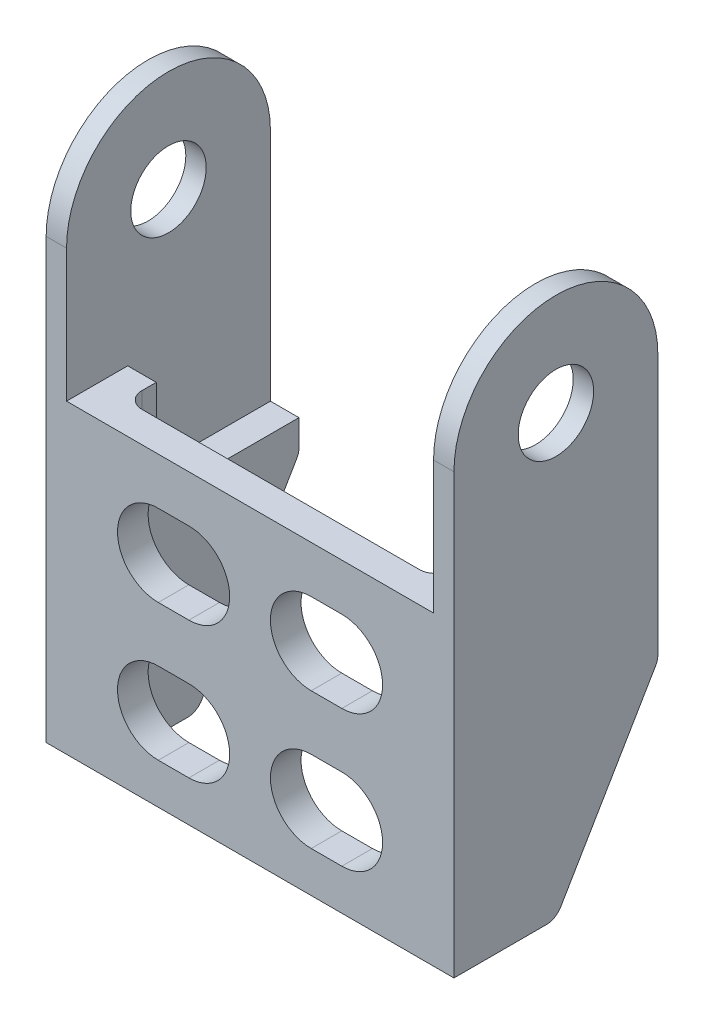
SolidWorks part; units mm, degrees
material "PLA+"
ref_plane "Front Plane" through (0, 0, 0) normal (0, 0, 1) x (1, 0, 0)
ref_plane "Top Plane" through (0, 0, 0) normal (0, 1, 0) x (1, 0, 0)
ref_plane "Right Plane" through (0, 0, 0) normal (1, 0, 0) x (0, 0, -1)
sketch "Sketch1" plane through (0, 0, 0) normal (0, 0, 1) x (1, 0, 0)
  line L1 (10, -7.5) -> (-10, -7.5)
  line L2 (10, -7.5) -> (10, 7.5)
  line L3 (10, 7.5) -> (-10, 7.5)
  line L4 (-10, -7.5) -> (-10, 7.5)
  line L5 (10, -7.5) -> (-10, 7.5) construction
  line L6 (10, 7.5) -> (-10, -7.5) construction
  point P0 (0, 0)
  dimension "D1" = 20
  dimension "D2" = 15
extrude "Boss-Extrude1" add sketch "Sketch1" along normal blind 1.5
sketch "Sketch2" plane through (10, 0, 0) normal (1, 0, 0) x (0, 0, -1)
  line L0 (-1.5, -7.5) -> (3.5, -7.5)
  line L1 (3.5, -7.5) -> (8.5, 1)
  line L2 (8.5, 1) -> (8.5, 14)
  line L4 (-1.5, 14) -> (-1.5, 7.5)
  arc A0 (8.5, 14) -> (-1.5, 14) centre (3.5, 14) ccw
  circle A1 centre (3.5, 14) radius 1.85
  point P9 (3.5, 19)
  line M1 (0, -7.5) -> (0, 7.5)
  line M2 (0, 7.5) -> (-1.5, 7.5)
  dimension "D3" = 10
  dimension "D5" = 3.7
  dimension "D1" = 10
  dimension "D2" = 5
  dimension "D4" = 26.5
  dimension "D6" = 8.5
extrude "Boss-Extrude2" add sketch "Sketch2" against normal blind 2.4 contours L2 A0 L4 L0 L1 A1 M2 M1 region at (10, 6.4099, -3.6241)
sketch "Sketch3" plane through (7.6, 0, 0) normal (-1, 0, 0) x (0, 0, 1)
  line L0 (1.5, 7.5) -> (-1.5, 7.5)
  line L1 (-1.5, 7.5) -> (-1.5, 5.5)
  line L2 (-4.5, 2.5) -> (-8.5, 2.5)
  line L3 (-8.5, 2.5) -> (-8.5, 19.0437)
  line L4 (-8.5, 19.0437) -> (1.5, 19.0437)
  line L5 (1.5, 19.0437) -> (1.5, 7.5)
  line L6 (-8.5, 1) -> (-8.5, 14) construction
  line L7 (0, -7.5) -> (-3.5, -7.5) construction
  arc A0 (-4.5, 2.5) -> (-1.5, 5.5) centre (-4.5, 5.5) ccw
  dimension "D1" = 3
  dimension "D2" = 10
  dimension "D3" = 3
extrude "Cut-Extrude1" cut sketch "Sketch3" against normal blind 1.4
mirror "Mirror1" about plane through (0, 0, 0) normal (1, 0, 0) of "Cut-Extrude1", "Boss-Extrude2", "Boss-Extrude1"
fillet "Fillet1" radius 0.8 6 edges at (-8.8, 1, -8.5) (8.8, 1, -8.5) (8.8, -7.5, -3.5) (-8.8, -7.5, -3.5) (-7.6, 0, 0) (7.6, 0, 0)
sketch "Sketch4" plane through (0, 0, 1.5) normal (0, 0, 1) x (1, 0, 0)
  line L0 (-4.5, 3.2) -> (-3, 3.2) construction
  line L1 (-4.5, 5.2) -> (-3, 5.2)
  line L2 (-4.5, 1.2) -> (-3, 1.2)
  line L3 (3, 3.2) -> (4.5, 3.2) construction
  line L4 (3, 5.2) -> (4.5, 5.2)
  line L5 (3, 1.2) -> (4.5, 1.2)
  line L6 (-4.5, -3.5) -> (-3, -3.5) construction
  line L7 (-4.5, -1.5) -> (-3, -1.5)
  line L8 (-4.5, -5.5) -> (-3, -5.5)
  line L9 (3, -3.5) -> (4.5, -3.5) construction
  line L10 (3, -1.5) -> (4.5, -1.5)
  line L11 (3, -5.5) -> (4.5, -5.5)
  line L12 (0, 0) -> (0, 4.2) construction
  line L13 (-10, -7.5) -> (10, -7.5) construction
  line L14 (9, 7.5) -> (-9, 7.5) construction
  arc A0 (-4.5, 5.2) -> (-4.5, 1.2) centre (-4.5, 3.2) ccw
  arc A1 (-3, 1.2) -> (-3, 5.2) centre (-3, 3.2) ccw
  arc A2 (3, 5.2) -> (3, 1.2) centre (3, 3.2) ccw
  arc A3 (4.5, 1.2) -> (4.5, 5.2) centre (4.5, 3.2) ccw
  arc A4 (-4.5, -1.5) -> (-4.5, -5.5) centre (-4.5, -3.5) ccw
  arc A5 (-3, -5.5) -> (-3, -1.5) centre (-3, -3.5) ccw
  arc A6 (3, -1.5) -> (3, -5.5) centre (3, -3.5) ccw
  arc A7 (4.5, -5.5) -> (4.5, -1.5) centre (4.5, -3.5) ccw
  point P2 (-3.75, 3.2)
  point P7 (3.75, 3.2)
  point P14 (-3.75, -3.5)
  point P21 (3.75, -3.5)
  point P35 (-1, -3.5)
  point P37 (1, -3.5)
  point P38 (-1, 3.2)
  point P39 (-6.5, 3.2)
  dimension "D1" = 4
  dimension "D2" = 2
  dimension "D3" = 2.3
  dimension "D4" = 2
  dimension "D5" = 5.5
extrude "Cut-Extrude2" cut sketch "Sketch4" against normal up to surface (1.5 mm away) up to face at (0, 0, 0)
